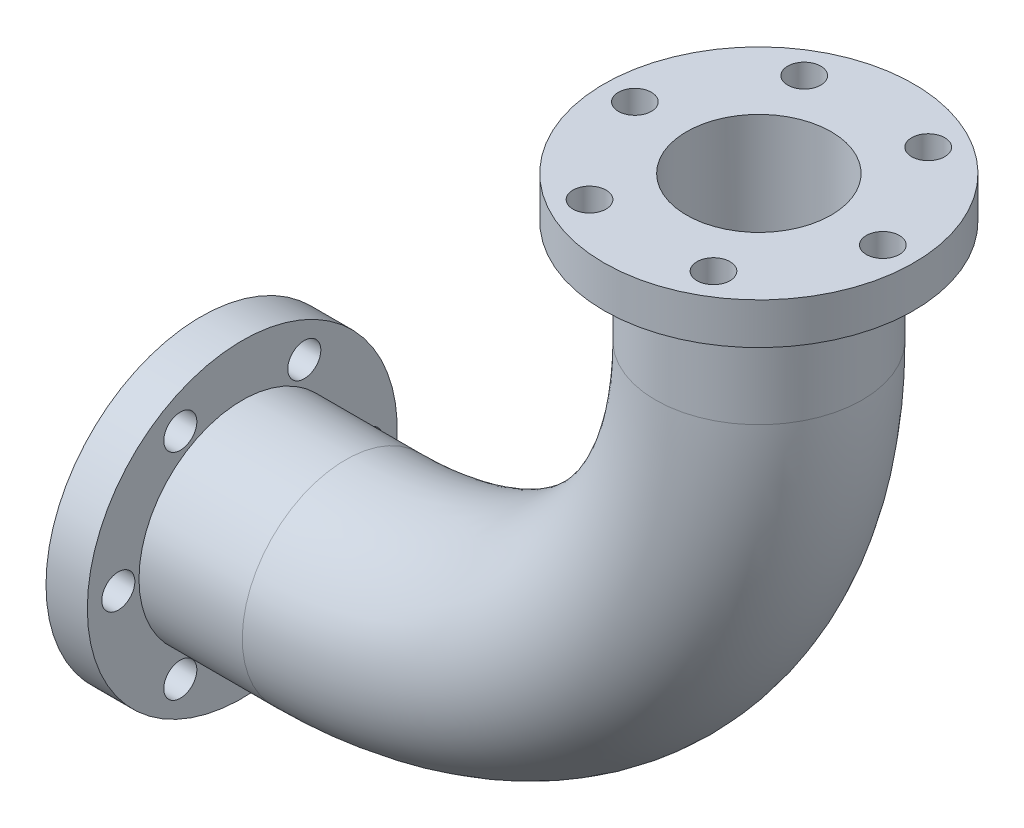
SolidWorks part; units mm, degrees
ref_plane "Front Plane" through (0, 0, 0) normal (0, 0, 1) x (1, 0, 0)
ref_plane "Top Plane" through (0, 0, 0) normal (0, 1, 0) x (1, 0, 0)
ref_plane "Right Plane" through (0, 0, 0) normal (1, 0, 0) x (0, 0, -1)
sketch "Sketch1" plane through (0, 0, 0) normal (0, 0, 1) x (1, 0, 0)
  line L0 (0, 0) -> (70, 0)
  line L1 (270, 200) -> (270, 270)
  arc A0 (70, 0) -> (270, 200) centre (70, 200) ccw
  point P5 (0, 0)
  dimension "D3" = 200
  dimension "D1" = 70
  dimension "D2" = 70
sketch "Sketch2" plane through (0, 0, 0) normal (1, 0, 0) x (0, 0, -1)
  circle A0 centre (0, 0) radius 50
  circle A1 centre (0, 0) radius 35
  dimension "D1" = 100
  dimension "D2" = 70
sweep "Sweep1" add profiles "Sketch2" path "Sketch1"
sketch "Sketch3" plane through (0, 270, 0) normal (0, 1, 0) x (1, 0, 0)
  circle A0 centre (270, 0) radius 75
  circle A1 centre (270, 0) radius 35 construction
  circle A2 centre (270, 0) radius 35
  dimension "D1" = 150
extrude "Boss-Extrude1" add sketch "Sketch3" against normal blind 20
sketch "Sketch4" plane through (0, 0, 0) normal (-1, 0, 0) x (0, 0, 1)
  circle A0 centre (0, 0) radius 75
  circle A1 centre (0, 0) radius 35 construction
  circle A2 centre (0, 0) radius 35
  dimension "D1" = 150
extrude "Boss-Extrude2" add sketch "Sketch4" against normal blind 20
hole_wizard "Hole1" positions "Sketch5" profile "Sketch6" legacy end condition up to next
sketch "Sketch5" plane through (0, 0, 0) normal (-1, 0, 0) x (0, 0, 1)
  point P0 (60, 0)
  point P4 (0, 0)
  dimension "D1" = 60
sketch "Sketch6" plane through (0, 0, 60) normal (0, 1, 0) x (0, 0, 1)
  line L0 (0, 0) -> (0, 20)
  line L1 (0, 20) -> (8, 20)
  line L2 (8, 20) -> (8, 0)
  line L3 (8, 0) -> (0, 0)
  line L4 (0, 110) -> (0, -10) construction
  dimension "Diameter" = 16
  dimension "Depth" = 20
pattern_circular "CirPattern1" count 6 over 360 about axis through (0, 0, 0) along (1, 0, 0) of "Hole1" reverse direction yes
hole_wizard "Hole2" positions "Sketch9" profile "Sketch10" legacy end condition up to next
sketch "Sketch9" plane through (0, 270, 0) normal (0, 1, 0) x (1, 0, 0)
  line L0 (270, 0) -> (330, 0) construction
  point P0 (330, 0)
  point P8 (0, 0)
  dimension "D1" = 60
sketch "Sketch10" plane through (330, 270, 0) normal (1, 0, 0) x (0, 0, 1)
  line L0 (0, 0) -> (0, 20)
  line L1 (0, 20) -> (8, 20)
  line L2 (8, 20) -> (8, 0)
  line L3 (8, 0) -> (0, 0)
  line L4 (0, 110) -> (0, -10) construction
  dimension "Diameter" = 16
  dimension "Depth" = 20
pattern_circular "CirPattern2" count 6 over 360 about axis through (270, 200, 0) along (0, 1, 0) of "Hole2" reverse direction yes
